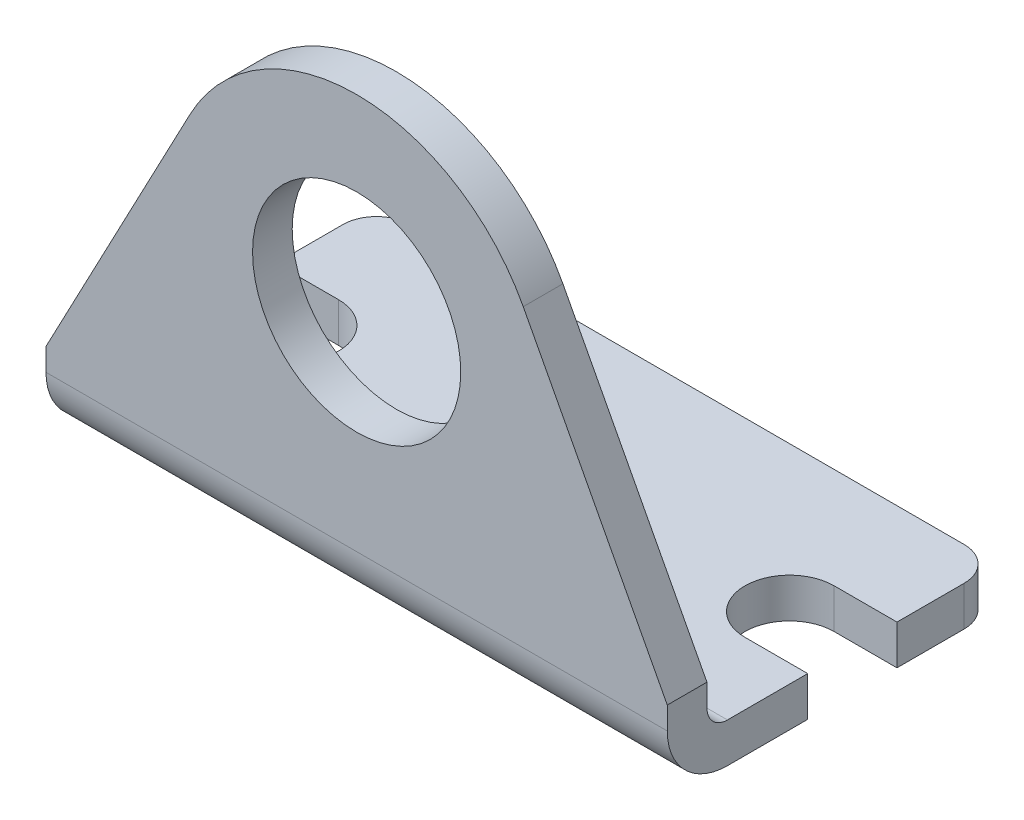
SolidWorks part; units mm, degrees
ref_plane "Front" through (0, 0, 0) normal (0, 0, 1) x (1, 0, 0)
ref_plane "Top" through (0, 0, 0) normal (0, 1, 0) x (1, 0, 0)
ref_plane "Right" through (0, 0, 0) normal (1, 0, 0) x (0, 0, -1)
sketch "Sketch0" plane through (0, 0, 0) normal (0, 0, 1) x (1, 0, 0)
  line L0 (0, 0) -> (0, 35.052) construction
  line L13 (-23.876, 0) -> (23.876, 0) construction
  line L14 (-23.876, 6.35) -> (-23.876, 0) construction
  circle A2 centre (0, 20.574) radius 8.001 construction
  point P3 (-23.876, 3.048)
  point P13 (0, 35.052)
  dimension "D" = 16.002
  dimension "B" = 47.752
  dimension "L" = 6.35
  dimension "H" = 3.048
  dimension "G" = 20.574
  dimension "A" = 35.052
sketch "Sketch00" plane through (0, 0, 0) normal (0, 1, 0) x (1, 0, 0)
  line L0 (0, 0) -> (0, 14.224) construction
  line L1 (-23.876, 25.4) -> (-23.876, 0) construction
  line L2 (-19.05, 14.224) -> (19.05, 14.224) construction
  line L3 (19.05, 17.653) -> (19.05, 10.795) construction
  line L4 (-23.876, 0) -> (23.876, 0) construction
  line L5 (-23.876, 0) -> (23.876, 0) construction
  point P9 (0, 14.224)
  dimension "C" = 25.4
  dimension "F" = 14.224
  dimension "K" = 38.1
  dimension "E" = 6.858
sketch "Sketch1" plane through (0, 0, 0) normal (0, 0, 1) x (1, 0, 0)
  line L0 (-23.876, 6.35) -> (-12.8046, 27.3309)
  line L2 (12.8046, 27.3309) -> (23.876, 6.35)
  line L3 (23.876, 6.35) -> (23.876, 0)
  line L4 (23.876, 0) -> (-23.876, 0)
  line L5 (-23.876, 0) -> (-23.876, 6.35)
  arc A0 (-12.8046, 27.3309) -> (12.8046, 27.3309) centre (0, 20.574) cw
  circle A1 centre (0, 20.574) radius 8.001
  circle A2 centre (0, 20.574) radius 8.001 construction
  point P7 (0, 35.052)
extrude "Boss-Extrude1" add sketch "Sketch1" against normal blind 3.048
sketch "Sketch2" plane through (0, 0, 0) normal (0, -1, 0) x (1, 0, 0)
  line L0 (23.876, -10.795) -> (19.05, -10.795)
  line L1 (-21.2937, -25.4) -> (21.2937, -25.4)
  line L2 (-23.876, -22.8177) -> (-23.876, -17.653)
  line L3 (-23.876, 0) -> (23.876, 0)
  line L4 (23.876, -22.8177) -> (23.876, -17.653)
  line L5 (23.876, -17.653) -> (19.05, -17.653)
  line L6 (23.876, -10.795) -> (23.876, 0)
  line L7 (-23.876, -10.795) -> (-23.876, 0)
  line L8 (-19.05, -10.795) -> (-23.876, -10.795)
  line L9 (21.2937, -25.4) -> (21.2937, -22.8177) construction
  line L10 (-19.05, -17.653) -> (-23.876, -17.653)
  line L11 (21.2937, -22.8177) -> (21.2937, -20.2353) construction
  line L12 (21.2937, -20.2353) -> (21.2937, -17.653) construction
  line L13 (19.05, -17.653) -> (19.05, -10.795) construction
  arc A0 (19.05, -10.795) -> (19.05, -17.653) centre (19.05, -14.224) ccw
  arc A1 (-19.05, -10.795) -> (-19.05, -17.653) centre (-19.05, -14.224) cw
  arc A2 (-21.2937, -25.4) -> (-23.876, -22.8177) centre (-21.2937, -22.8177) cw
  arc A3 (21.2937, -25.4) -> (23.876, -22.8177) centre (21.2937, -22.8177) ccw
extrude "Boss-Extrude2" add sketch "Sketch2" against normal up to vertex (3.048 mm away) up to point (-23.876, 3.048, 0)
fillet "Fillet1" radius 1.5748 1 edges at (0, 3.048, -3.048)
fillet "Fillet2" radius 4.6228 1 edges at (0, 0, 0)
sketch "Sketch3" plane through (-23.876, 0, 0) normal (-1, 0, 0) x (0, 0, 1)
  line L0 (-12.3317, 3.048) -> (-3.048, 12.3317)
  line L1 (-4.6228, 3.048) -> (-10.795, 3.048) construction
  line L2 (-3.048, 6.35) -> (-3.048, 4.6228) construction
  line L3 (-3.048, 12.3317) -> (-3.048, 4.6228)
  line L4 (-4.6228, 3.048) -> (-12.3317, 3.048)
  arc A0 (-4.6228, 3.048) -> (-3.048, 4.6228) centre (-4.6228, 4.6228) ccw construction
  arc A1 (-4.6228, 3.048) -> (-3.048, 4.6228) centre (-4.6228, 4.6228) ccw
  dimension "D1" = 45
  dimension "D2" = 9.2837
extrude "K296" [suppressed] add sketch "Sketch3" against normal blind 3.048
mirror "Mirror1" [suppressed] about plane through (0, 0, 0) normal (1, 0, 0)
sketch "Sketch4" plane through (0, 0, 0) normal (1, 0, 0) x (0, 0, -1)
  line L0 (3.048, 9.3988) -> (9.3988, 3.048)
  line L1 (3.048, 6.35) -> (3.048, 4.6228) construction
  line L2 (4.6228, 3.048) -> (10.795, 3.048) construction
  line L3 (3.048, 9.3988) -> (3.048, 4.6228)
  line L4 (4.6228, 3.048) -> (9.3988, 3.048)
  arc A0 (3.048, 4.6228) -> (4.6228, 3.048) centre (4.6228, 4.6228) ccw construction
  arc A1 (3.048, 4.6228) -> (4.6228, 3.048) centre (4.6228, 4.6228) ccw
  dimension "D1" = 8.9814
extrude "K297" [suppressed] add sketch "Sketch4" along normal mid plane 3.048 from offset 11.1125 offset against normal yes
mirror "Mirror2" [suppressed] about plane through (0, 0, 0) normal (1, 0, 0)
equation "\"D1@Boss-Extrude1\" = \"H@Sketch1\""
equation "\"D1@Fillet2\" = \"D1@Fillet1\" + \"H@Sketch0\""
equation "\"D1@K296\"= \"H@Sketch0\""
equation "\"D1@K297\" = \"H@Sketch0\""
